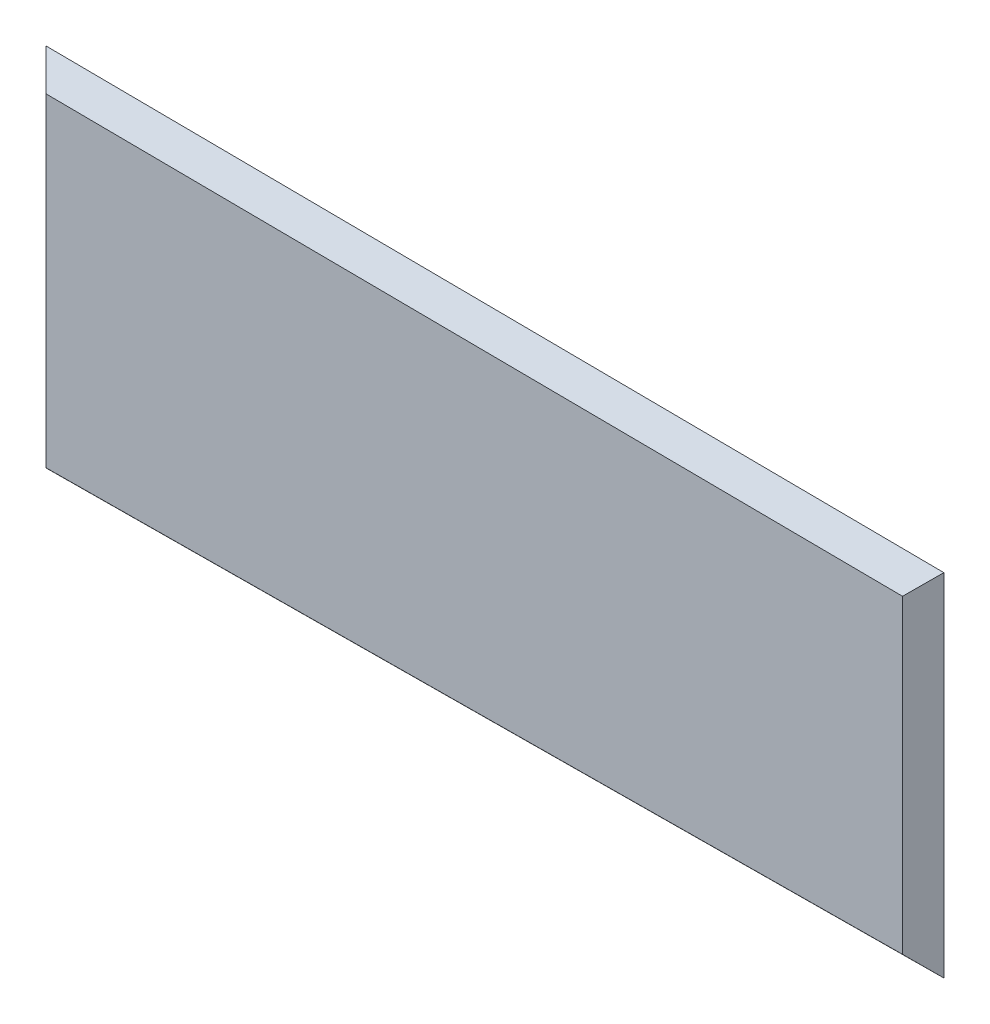
SolidWorks part; units mm, degrees
ref_plane "Ebene vorne" through (0, 0, 0) normal (0, 0, 1) x (1, 0, 0)
ref_plane "Ebene oben" through (0, 0, 0) normal (0, 1, 0) x (1, 0, 0)
ref_plane "Ebene rechts" through (0, 0, 0) normal (1, 0, 0) x (0, 0, -1)
sketch "Skizze1" plane through (0, 0, 0) normal (0, 0, 1) x (1, 0, 0)
  line L0 (-655.2882, 0) -> (689.2934, 0) construction
  line L1 (0, 379.1113) -> (0, -337.7537) construction
  line L2 (-434.7143, -88.5) -> (-434.7143, 88.5)
  line L3 (-434.7143, 88.5) -> (0, 85)
  line L4 (0, 85) -> (0, -85)
  line L6 (-434.7143, -88.5) -> (0, -85)
  point P10 (0, 0)
  point P11 (-434.7143, 0)
  dimension "D1" = 177
  dimension "D2" = 170
extrude "Aufsatz-Linear austragen1" add sketch "Skizze1" along normal blind 10
chamfer "Fase1" distance 10 angle 45 4 edges at (-434.7143, 0, 10) (-217.3572, 86.75, 10) (0, 0, 10) (-217.3572, -86.75, 10)
